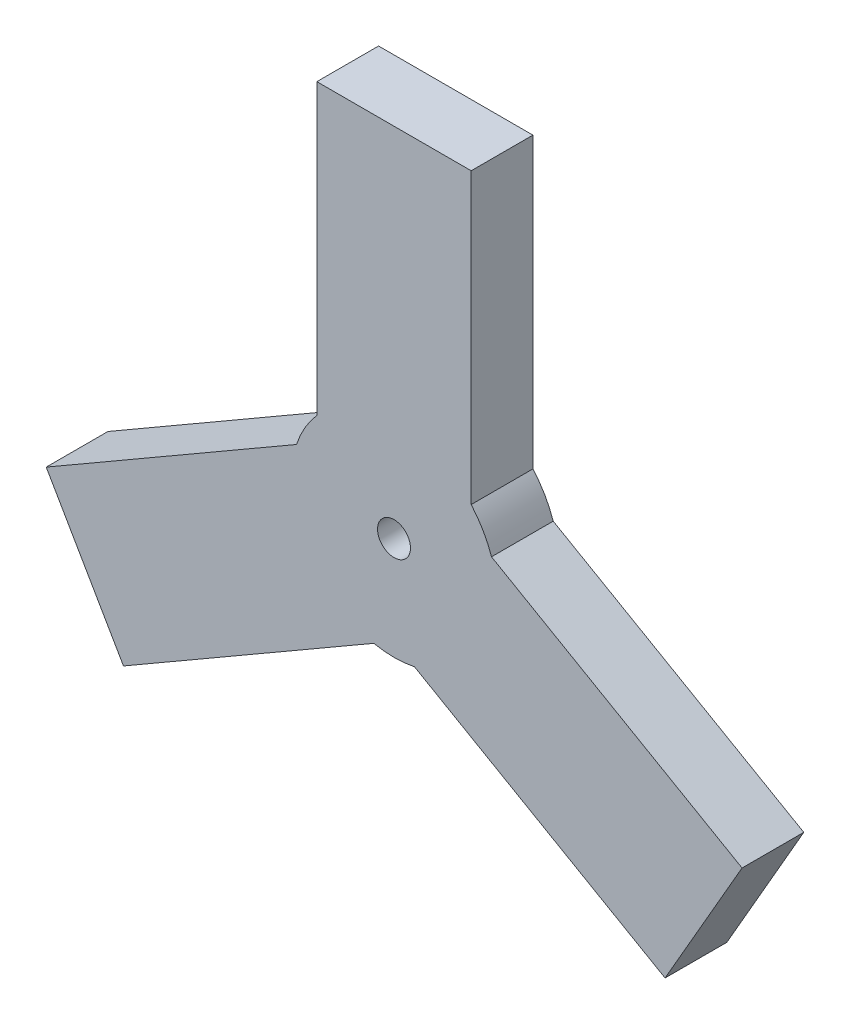
SolidWorks part; units mm, degrees
ref_plane "Front Plane" through (0, 0, 0) normal (0, 0, 1) x (1, 0, 0)
ref_plane "Top Plane" through (0, 0, 0) normal (0, 1, 0) x (1, 0, 0)
ref_plane "Right Plane" through (0, 0, 0) normal (1, 0, 0) x (0, 0, -1)
sketch "Sketch2" plane through (0, 0, 0) normal (0, 0, 1) x (1, 0, 0)
  line L0 (0, -167.7125) -> (0, 44.0843) construction
  line L1 (-12.0402, 4.0402) -> (-42.9308, -13.8239)
  line L2 (-10.9804, -6.35) -> (0, 12.7) construction
  line L3 (0, 12.7) -> (11.0076, -6.3343) construction
  line L4 (11.0076, -6.3343) -> (-10.9804, -6.35) construction
  line L5 (-9.525, 8.4003) -> (-9.525, 44.0843)
  line L6 (-9.525, 44.0843) -> (9.525, 44.0843)
  line L7 (9.525, 44.0843) -> (9.525, 8.4003)
  line L8 (-38.1624, -22.0694) -> (158.954, 91.9233) construction
  line L9 (-125.502, 72.2201) -> (38.2095, -21.9877) construction
  line L10 (-42.9308, -13.8239) -> (-33.394, -30.3149)
  line L11 (-33.394, -30.3149) -> (-2.5035, -12.4508)
  line L12 (12.0316, 4.0659) -> (42.9603, -13.732)
  line L13 (42.9603, -13.732) -> (33.4588, -30.2434)
  line L14 (33.4588, -30.2434) -> (2.5301, -12.4454)
  arc A0 (-2.5035, -12.4508) -> (2.5301, -12.4454) centre (0, 0) ccw
  circle A1 centre (0, 0) radius 2.032
  arc A2 (12.0316, 4.0659) -> (9.525, 8.4003) centre (0, 0) ccw
  arc A3 (-9.525, 8.4003) -> (-12.0402, 4.0402) centre (0, 0) ccw
  circle A4 centre (0, 0) radius 12.7 construction
  point P22 (39.7348, -22.9503)
  dimension "D3" = 25.4
  dimension "D4" = 4.064
  dimension "D1" = 60
  dimension "D2" = 60
  dimension "D5" = 35.684
  dimension "D6" = 19.05
  dimension "D7" = 120.041
extrude "Boss-Extrude1" add sketch "Sketch2" along normal blind 7.62
